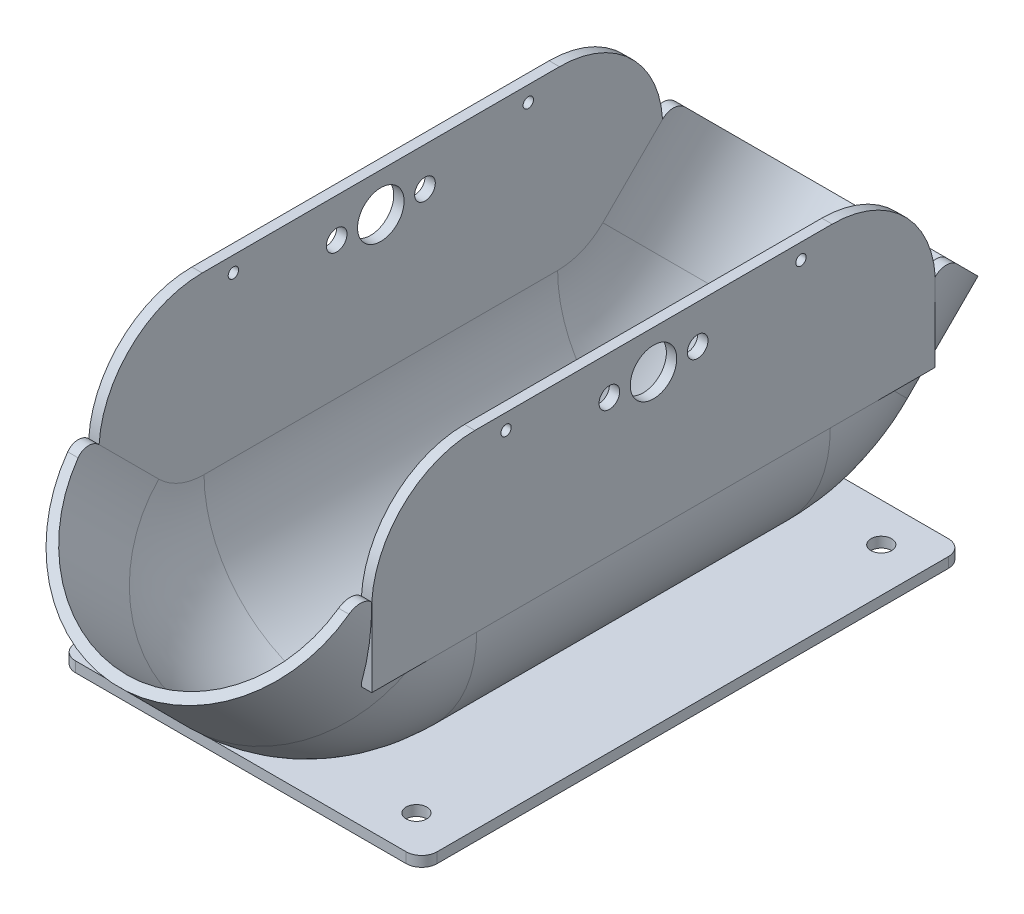
SolidWorks part; units mm, degrees
ref_plane "Front Plane" through (0, 0, 0) normal (0, 0, 1) x (1, 0, 0)
ref_plane "Top Plane" through (0, 0, 0) normal (0, 1, 0) x (1, 0, 0)
ref_plane "Right Plane" through (0, 0, 0) normal (1, 0, 0) x (0, 0, -1)
sketch "Sketch1" plane through (0, 0, 0) normal (0, 0, 1) x (1, 0, 0)
  line L2 (-25.4, 0) -> (-27.4, 0)
  line L3 (25.4, 0) -> (27.4, 0)
  line L4 (-27.3269, 2) -> (27.3269, 2) construction
  line L5 (-25.4, 0) -> (25.4, 0) construction
  arc A0 (-25.4, 0) -> (25.4, 0) centre (0, 0) ccw
  arc A1 (-27.4, 0) -> (27.4, 0) centre (0, 0) ccw
  arc A2 (-27.3269, 2) -> (27.3269, 2) centre (0, 0) ccw construction
  dimension "D1" = 50.8
  dimension "D2" = 2
sketch "Sketch3" plane through (0, 0, 0) normal (1, 0, 0) x (0, 0, -1)
  line L0 (-34.2315, -27.6128) -> (34.2315, -27.6128)
  line L2 (0, 0) -> (0, -27.4) construction
  line L3 (62.5157, -15.8971) -> (76.2, -2.2128)
  line L4 (0, -27.6128) -> (0, 7.0661) construction
  line L5 (-62.5157, -15.8971) -> (-76.2, -2.2128)
  arc A0 (34.2315, -27.6128) -> (62.5157, -15.8971) centre (34.2315, 12.3872) ccw
  arc A1 (-34.2315, -27.6128) -> (-62.5157, -15.8971) centre (-34.2315, 12.3872) cw
  point P7 (50.8, -27.6128)
  point P14 (-50.8, -27.6128)
  dimension "D3" = 40
  dimension "D1" = 45
  dimension "D2" = 50.8
  dimension "D4" = 25.4
sweep "Sweep2" add profiles "Sketch1" path "Sketch3"
sketch "Sketch4" plane through (0, 0, 0) normal (0, 1, 0) x (1, 0, 0)
  circle A0 centre (-26.5, 45) radius 2
  circle A1 centre (26.5, 45) radius 2
  circle A2 centre (-26.5, -45) radius 2
  circle A3 centre (26.5, -45) radius 2
  dimension "D3" = 4
  dimension "D4" = 4
  dimension "D5" = 4
  dimension "D6" = 4
  dimension "D1" = 53
  dimension "D2" = 90
  dimension "D7" = 45
  dimension "D8" = 26.5
sketch "Sketch5" plane through (0, 0, 0) normal (0, 1, 0) x (1, 0, 0)
  line L1 (-35, 52.5) -> (35, 52.5)
  line L2 (-35, 52.5) -> (-35, -52.5)
  line L3 (-35, -52.5) -> (35, -52.5)
  line L4 (35, 52.5) -> (35, -52.5)
  dimension "D1" = 105
  dimension "D2" = 52.5
  dimension "D3" = 70
  dimension "D4" = 35
ref_plane "Plane2" through (0, -27.4, 0) normal (0, -1, 0) x (-1, 0, 0)
sketch "Sketch6" plane through (0, -27.4, 0) normal (0, -1, 0) x (-1, 0, 0)
  line L0 (-35, 52.5) -> (35, 52.5)
  line L1 (-35, 52.5) -> (-35, -52.5)
  line L2 (-35, -52.5) -> (35, -52.5)
  line L3 (35, 52.5) -> (35, -52.5)
  dimension "D1" = 35
  dimension "D2" = 52.5
  dimension "D3" = 70
  dimension "D4" = 105
extrude "Boss-Extrude1" add sketch "Sketch6" against normal blind 2
extrude "Cut-Extrude1" cut sketch "Sketch4" against normal blind 5 from surface starting at face at (0, -25.4, 0)
fillet "Fillet1" radius 3 4 edges at (26.4, 17.3124, -56.6748) (-26.4, 17.3124, -56.6748) (26.4, 17.3124, 56.6748) (-26.4, 17.3124, 56.6748)
fillet "Fillet2" radius 3 4 edges at (35, -26.4, -52.5) (-35, -26.4, -52.5) (35, -26.4, 52.5) (-35, -26.4, 52.5)
sketch "Sketch7" plane through (0, 0, 0) normal (0, 1, 0) x (1, 0, 0)
  line L1 (-27.4, 54.5534) -> (-25.4, 54.5534)
  line L2 (-27.4, 54.5534) -> (-27.4, -54.5534)
  line L3 (-27.4, -54.5534) -> (-25.4, -54.5534)
  line L4 (-25.4, 54.5534) -> (-25.4, -54.5534)
ref_plane "Plane3" through (0, 34, 0) normal (0, 1, 0) x (1, 0, 0)
sketch "Sketch8" plane through (0, 0, 0) normal (0, 0, 1) x (1, 0, 0)
  line L0 (-27.3859, 16.0697) -> (-27.4, 0)
  arc A0 (-27.4, 0) -> (-16.5328, -21.8501) centre (-0.0482, -0.024) ccw
  arc A1 (-27.4, 0) -> (-10.2762, -25.4) centre (0, 0) ccw construction
sketch "Sketch9" plane through (0, 34, 0) normal (0, 1, 0) x (1, 0, 0)
  line L0 (0, 0) -> (0, 51.2715) construction
  line L1 (-27.4, 54.5534) -> (-25.4, 54.5534)
  line L2 (-27.4, 54.5534) -> (-27.4, -54.5534)
  line L3 (-27.4, -54.5534) -> (-25.4, -54.5534)
  line L4 (-25.4, 54.5534) -> (-25.4, -54.5534)
  line L5 (27.4, -54.5534) -> (25.4, -54.5534)
  line L6 (25.4, 54.5534) -> (25.4, -54.5534)
  line L7 (27.4, 54.5534) -> (25.4, 54.5534)
  line L8 (27.4, 54.5534) -> (27.4, -54.5534)
extrude "Boss-Extrude2" add sketch "Sketch9" against normal up to surface (34 mm away) up to face at (-26.4, 0, 0)
sketch "Sketch10" plane through (-27.4, 0, 0) normal (-1, 0, 0) x (0, 0, 1)
  line L0 (0, 0) -> (0, 20.3745) construction
  line L1 (-54.5534, 0) -> (54.5534, 0) construction
  line L2 (-54.5534, 34) -> (54.5534, 34) construction
  circle A0 centre (-8.55, 26.5) radius 2
  circle A1 centre (8.55, 26.5) radius 2
  circle A2 centre (0, 26.5) radius 4.5
  dimension "D1" = 4
  dimension "D4" = 9
  dimension "D2" = 7.5
  dimension "D3" = 8.55
extrude "Cut-Extrude2" cut sketch "Sketch10" against normal through all
sketch "Sketch11" plane through (-27.4, 0, 0) normal (-1, 0, 0) x (0, 0, 1)
  line L0 (38.5, 34) -> (-38.5, 34) construction
  line L1 (0, 25.9541) -> (0, 38.1257) construction
  circle A0 centre (-28.55, 31) radius 1
  circle A1 centre (-8.55, 26.5) radius 2 construction
  circle A2 centre (28.55, 31) radius 1
  dimension "D1" = 2
  dimension "D3" = 20
  dimension "D2" = 3
extrude "Cut-Extrude4" cut sketch "Sketch11" against normal through all
fillet "Fillet4" radius 20 4 edges at (26.4, 34, 54.5534) (-26.4, 34, 54.5534) (26.4, 34, -54.5534) (-26.4, 34, -54.5534)
equation "\"D7@Sketch4\"=90/2"
equation "\"D8@Sketch4\"=53/2"
equation "\"D2@Sketch5\"=105/2"
equation "\"D4@Sketch5\"=35"
